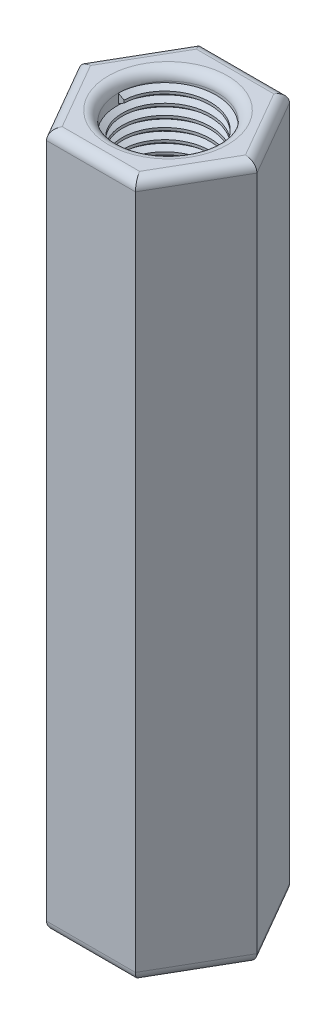
SolidWorks part; units mm, degrees
ref_plane "Front Plane" through (0, 0, 0) normal (0, 0, 1) x (1, 0, 0)
ref_plane "Top Plane" through (0, 0, 0) normal (0, 1, 0) x (1, 0, 0)
ref_plane "Right Plane" through (0, 0, 0) normal (1, 0, 0) x (0, 0, -1)
sketch "草图1" plane through (0, 0, 0) normal (0, 1, 0) x (1, 0, 0)
  line L1 (2.6847, 0) -> (1.3423, 2.325)
  line L2 (1.3423, 2.325) -> (-1.3423, 2.325)
  line L3 (-1.3423, 2.325) -> (-2.6847, 0)
  line L4 (-2.6847, 0) -> (-1.3423, -2.325)
  line L5 (-1.3423, -2.325) -> (1.3423, -2.325)
  line L6 (1.3423, -2.325) -> (2.6847, 0)
  circle A0 centre (0, 0) radius 2.325 construction
  circle A1 centre (0, 0) radius 1.5
  dimension "D2" = 3
  dimension "D1" = 4.65
extrude "凸台-拉伸1" add sketch "草图1" along normal blind 21
fillet "圆角3" radius 0.3 14 edges at (0, 0, 1.5) (2.0135, 0, -1.1625) (0, 0, -2.325) (-2.0135, 0, -1.1625) (-2.0135, 0, 1.1625) (0, 0, 2.325) (2.0135, 0, 1.1625) (0, 21, 1.5) (0, 21, 2.325) (-2.0135, 21, 1.1625) (-2.0135, 21, -1.1625) (0, 21, -2.325) (2.0135, 21, -1.1625) (2.0135, 21, 1.1625)
thread "螺纹线1" pitch 0.3175 method extrude profile "螺纹线轮廓1" start angle 0, offset 0, length 6, pitch 0.3175, diameter 3
ref_plane "基准面1" through (1.5, 0.3, 0) normal (0, 0, 1) x (1, 0, 0)
sketch "螺纹线轮廓1" plane through (1.5, 0.3, 0) normal (0, 0, 1) x (1, 0, 0)
  line L0 (0, 0) -> (0, 0.3175) construction
  line L11 (0, 0) -> (0, 0.2778)
  line L12 (0, 0.2778) -> (-0.1719, 0.1786)
  line L13 (-0.1719, 0.1786) -> (-0.1719, 0.0992)
  line L15 (-0.1719, 0.0992) -> (0, 0)
  line L17 (-0.1719, 0.1389) -> (0, 0.1389) construction
  point P2 (0, 0)
  dimension "Pitch" = 0.3175
  dimension "Profile_Angle" = 60
  dimension "Profile_Land" = 0.0794
  dimension "Profile_Height" = 0.1719
thread "螺纹线2" pitch 0.3175 method extrude profile "螺纹线轮廓2" start angle 0, offset 0, length 6, pitch 0.3175, diameter 3
ref_plane "基准面2" through (-1.5, 20.7, 0) normal (0, 0, 1) x (-1, 0, 0)
sketch "螺纹线轮廓2" plane through (-1.5, 20.7, 0) normal (0, 0, 1) x (-1, 0, 0)
  line L0 (0, 0) -> (0, 0.3175) construction
  line L11 (0, 0) -> (0, 0.2778)
  line L12 (0, 0.2778) -> (-0.1719, 0.1786)
  line L13 (-0.1719, 0.1786) -> (-0.1719, 0.0992)
  line L15 (-0.1719, 0.0992) -> (0, 0)
  line L17 (-0.1719, 0.1389) -> (0, 0.1389) construction
  point P2 (0, 0)
  dimension "Pitch" = 0.3175
  dimension "Profile_Angle" = 60
  dimension "Profile_Land" = 0.0794
  dimension "Profile_Height" = 0.1719
equation "\"4。65\"=37.0326"
